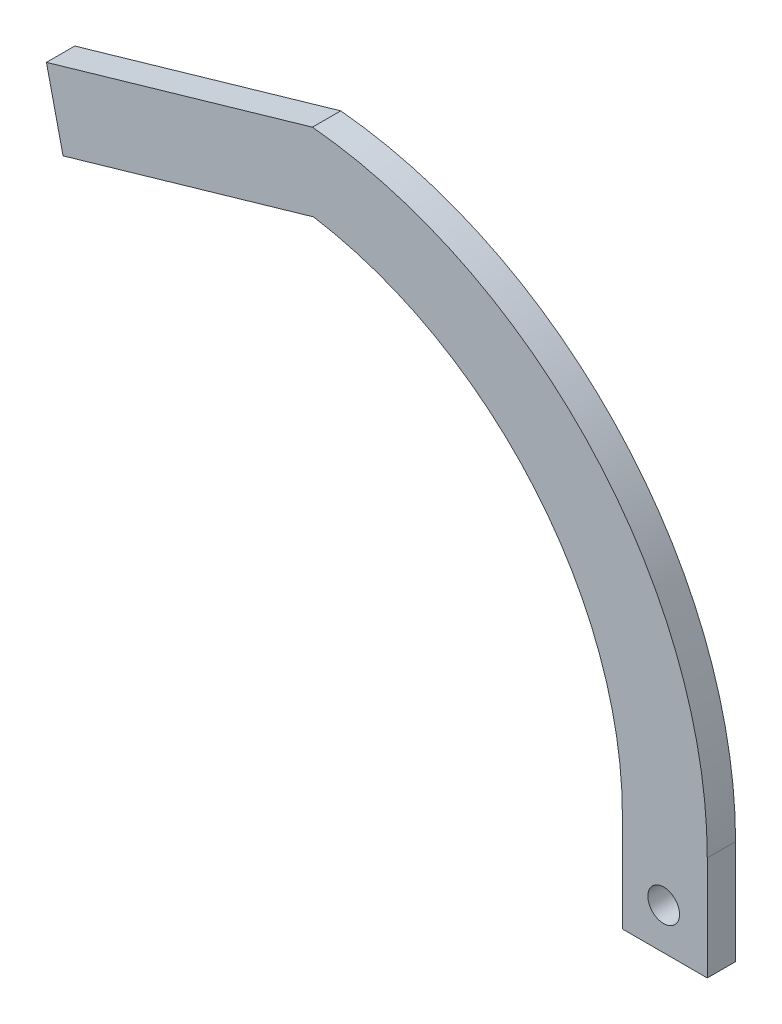
SolidWorks part; units mm, degrees
ref_plane "Front Plane" through (0, 0, 0) normal (0, 0, 1) x (1, 0, 0)
ref_plane "Top Plane" through (0, 0, 0) normal (0, 1, 0) x (1, 0, 0)
ref_plane "Right Plane" through (0, 0, 0) normal (1, 0, 0) x (0, 0, -1)
sketch "Sketch1" plane through (0, 0, 0) normal (0, 0, 1) x (1, 0, 0)
  line L0 (-106.2032, 123.8526) -> (-153.9564, 110.0545)
  line L1 (-106.0077, 109.999) -> (-150.9724, 97.0066)
  line L2 (-50.5678, 44.7987) -> (-50.5678, 27.0187)
  line L3 (-50.5678, 27.0187) -> (-35.3278, 27.0187)
  line L4 (-35.3278, 45.6917) -> (-35.3278, 27.0187)
  line L5 (-150.9724, 97.0066) -> (-153.9564, 110.0545)
  arc A0 (-50.5678, 44.7987) -> (-106.0077, 109.999) centre (-116.6273, 44.7987) ccw
  arc A1 (-35.3278, 45.6917) -> (-106.2032, 123.8526) centre (-113.8632, 45.6917) ccw
  dimension "D4" = 78.5354
  dimension "D5" = 66.0595
  dimension "D7" = 59.69
  dimension "D1" = 17.78
  dimension "D2" = 15.24
  dimension "D3" = 13.855
  dimension "D6" = 35.3278
extrude "Boss-Extrude1" add sketch "Sketch1" along normal mid plane 5.08
sketch "Sketch2" plane through (0, 0, 2.54) normal (0, 0, 1) x (1, 0, 0)
  line L0 (-50.5678, 27.0187) -> (-35.3278, 27.0187) construction
  line L1 (-50.5678, 44.7987) -> (-50.5678, 27.0187) construction
  circle A0 centre (-43.1522, 34.4122) radius 2.8448
  point P2 (-42.9478, 27.0187)
  dimension "D1" = 5.6896
  dimension "D2" = 7.3963
  dimension "D3" = 7.4156
extrude "Cut-Extrude1" cut sketch "Sketch2" against normal up to surface (5.08 mm away) up to face at (-82.733, 76.1634, -2.54)
